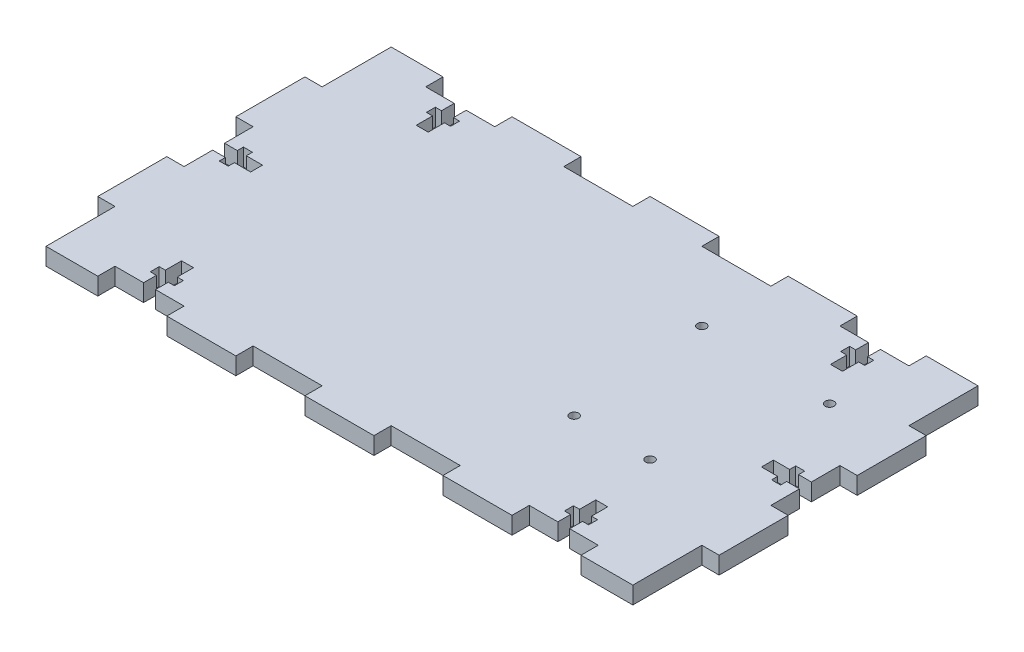
SolidWorks part; units mm, degrees
ref_plane "Front Plane" through (0, 0, 0) normal (0, 0, 1) x (1, 0, 0)
ref_plane "Top Plane" through (0, 0, 0) normal (0, 1, 0) x (1, 0, 0)
ref_plane "Right Plane" through (0, 0, 0) normal (1, 0, 0) x (0, 0, -1)
sketch "Sketch1" plane through (0, 0, 0) normal (0, 1, 0) x (1, 0, 0)
  line L1 (0, 0) -> (228.6, 0)
  line L2 (0, 0) -> (0, 127)
  line L3 (0, 127) -> (228.6, 127)
  line L4 (228.6, 0) -> (228.6, 127)
  dimension "D1" = 127
  dimension "D2" = 228.6
extrude "Boss-Extrude1" add sketch "Sketch1" along normal blind 6.35
sketch "Sketch2" plane through (0, 6.35, 0) normal (0, 1, 0) x (1, 0, 0)
  line L1 (0, 127) -> (6.35, 127)
  line L2 (0, 127) -> (0, 101.6)
  line L3 (0, 101.6) -> (6.35, 101.6)
  line L4 (6.35, 127) -> (6.35, 101.6)
  dimension "D1" = 25.4
  dimension "D2" = 6.35
extrude "Cut-Extrude1" cut sketch "Sketch2" against normal blind 6.35
pattern_linear "LPattern1" count 3 spacing 50.8 along (0, 0, 1) count 2 spacing 222.25 along (1, 0, 0) of "Cut-Extrude1"
sketch "Sketch3" plane through (0, 6.35, 0) normal (0, 1, 0) x (1, 0, 0)
  line L0 (6.35, 0) -> (222.25, 0) construction
  line L1 (25.4, 0) -> (50.8, 0)
  line L2 (25.4, 0) -> (25.4, 6.35)
  line L3 (25.4, 6.35) -> (50.8, 6.35)
  line L4 (50.8, 0) -> (50.8, 6.35)
  line L5 (0, 50.8) -> (0, 25.4) construction
  dimension "D1" = 25.4
  dimension "D2" = 6.35
  dimension "D3" = 25.4
extrude "Cut-Extrude2" cut sketch "Sketch3" against normal blind 6.35
pattern_linear "LPattern2" count 4 spacing 50.8 along (1, 0, 0) count 2 spacing 120.65 along (0, 0, -1) of "Cut-Extrude2"
ref_plane "Plane1" through (0, 0, -63.5) normal (0, 0, 1) x (1, 0, 0)
ref_plane "Plane2" through (114.3, 0, 0) normal (1, 0, 0) x (0, 0, -1)
sketch "Sketch4" plane through (0, 6.35, 0) normal (0, 1, 0) x (1, 0, 0)
  line L0 (222.25, 76.2) -> (222.25, 50.8) construction
  line L1 (222.25, 65.6971) -> (208.28, 65.6971)
  line L2 (222.25, 65.6971) -> (222.25, 61.3029)
  line L3 (222.25, 61.3029) -> (208.28, 61.3029)
  line L4 (208.28, 65.6971) -> (208.28, 61.3029)
  line L5 (228.6, 76.2) -> (222.25, 76.2) construction
  line L7 (214.249, 67.945) -> (217.551, 67.945)
  line L8 (214.249, 67.945) -> (214.249, 59.055)
  line L9 (214.249, 59.055) -> (217.551, 59.055)
  line L10 (217.551, 67.945) -> (217.551, 59.055)
  point P6 (222.25, 63.5)
  point P13 (215.9, 59.055)
  point P14 (217.551, 63.5)
  dimension "D1" = 13.97
  dimension "D2" = 4.3942
  dimension "D3" = 12.7
  dimension "D4" = 3.302
  dimension "D5" = 6.35
  dimension "D6" = 8.89
  dimension "D7" = 12.7
extrude "Cut-Extrude3" cut sketch "Sketch4" against normal blind 8.89 contours L1 L4 L3 L2 | L7 L10 L9 L8
mirror "Mirror1" about plane through (114.3, 0, 0) normal (1, 0, 0) of "Cut-Extrude3"
sketch "Sketch5" plane through (0, 6.35, 0) normal (0, 1, 0) x (1, 0, 0)
  line L0 (50.8, 6.35) -> (25.4, 6.35) construction
  line L1 (35.9029, 6.35) -> (40.2971, 6.35)
  line L2 (35.9029, 6.35) -> (35.9029, 20.32)
  line L3 (35.9029, 20.32) -> (40.2971, 20.32)
  line L4 (40.2971, 6.35) -> (40.2971, 20.32)
  line L5 (50.8, 0) -> (50.8, 6.35) construction
  line L6 (33.655, 14.351) -> (42.545, 14.351)
  line L7 (33.655, 14.351) -> (33.655, 11.049)
  line L8 (33.655, 11.049) -> (42.545, 11.049)
  line L9 (42.545, 14.351) -> (42.545, 11.049)
  point P6 (38.1, 20.32)
  point P12 (38.1, 11.049)
  point P15 (42.545, 12.7)
  dimension "D1" = 13.97
  dimension "D2" = 4.3942
  dimension "D3" = 12.7
  dimension "D4" = 3.302
  dimension "D5" = 8.89
  dimension "D6" = 12.7
  dimension "D7" = 6.35
extrude "Cut-Extrude4" cut sketch "Sketch5" against normal blind 30.48 contours L3 L4 L1 L2 | L7 L8 L9 L6
mirror "Mirror2" about plane through (114.3, 0, 0) normal (1, 0, 0) of "Cut-Extrude4"
mirror "Mirror3" about plane through (0, 0, -63.5) normal (0, 0, 1) of "Mirror2"
sketch "Sketch6" plane through (0, 6.35, 0) normal (0, 1, 0) x (1, 0, 0)
  line L0 (114.3, -21.2715) -> (114.3, 21.2715) construction
  line L1 (152.4, 95.25) -> (200.66, 95.25)
  line L2 (152.4, 95.25) -> (152.4, 43.18)
  line L3 (152.4, 43.18) -> (200.66, 43.18)
  line L4 (200.66, 95.25) -> (200.66, 43.18)
  line L5 (127, 120.65) -> (152.4, 120.65) construction
  dimension "D1" = 52.07
  dimension "D2" = 48.26
  dimension "D3" = 38.1
  dimension "D4" = 25.4
hole_wizard "#4 Clearance Hole1" positions "Sketch9" profile "Sketch8" hole size "#4" standard "ANSI Inch"
sketch "Sketch9" plane through (0, 6.35, 0) normal (0, 1, 0) x (1, 0, 0)
  line L0 (200.66, 95.25) -> (200.66, 43.18) construction
  line L1 (152.4, 95.25) -> (200.66, 95.25) construction
  line L2 (152.4, 43.18) -> (200.66, 43.18) construction
  line L3 (152.4, 95.25) -> (152.4, 43.18) construction
  point P0 (152.4, 95.25)
  point P2 (200.66, 93.98)
  point P4 (185.42, 43.18)
  point P6 (157.48, 43.18)
  dimension "D1" = 1.27
  dimension "D2" = 5.08
  dimension "D3" = 15.24
sketch "Sketch8" plane through (152.4, 6.35, -95.25) normal (1, 0, 0) x (0, 0, 1)
  line L0 (0, 0) -> (0, 11.1406)
  line L1 (0, 11.1406) -> (1.6319, 10.16)
  line L2 (1.6319, 10.16) -> (1.6319, 0)
  line L5 (1.6319, 0) -> (0, 0)
  line L10 (0, 11.1406) -> (-1.632, 10.16) construction
  line L11 (0, -6.35) -> (0, 107.95) construction
  dimension "Hole Dia." = 3.2639
  dimension "Hole Depth" = 10.16
  dimension "Drill Angle" = 118
